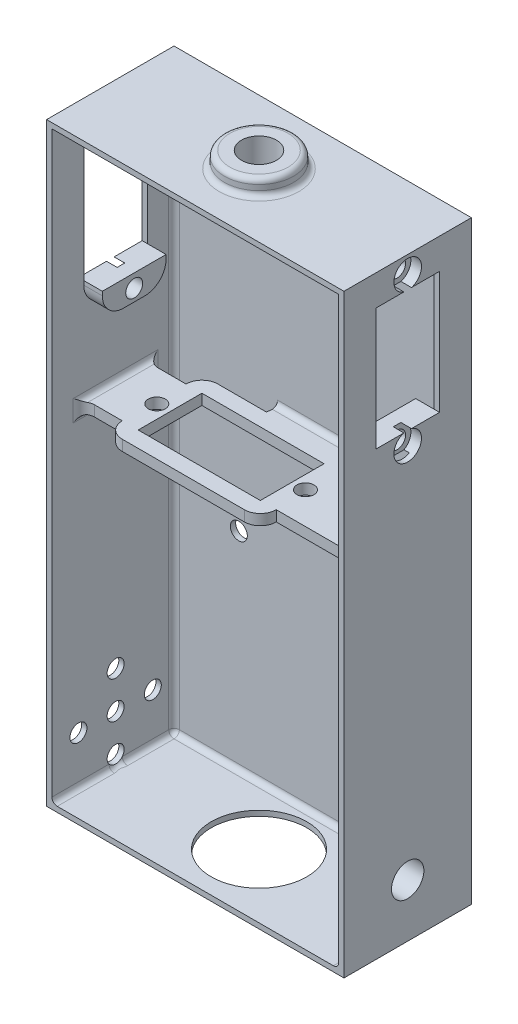
SolidWorks part; units mm, degrees
ref_plane "前视基准面" through (0, 0, 0) normal (0, 0, 1) x (1, 0, 0)
ref_plane "上视基准面" through (0, 0, 0) normal (0, 1, 0) x (1, 0, 0)
ref_plane "右视基准面" through (0, 0, 0) normal (1, 0, 0) x (0, 0, -1)
other "Configuration Table"
sketch "草图2" plane through (0, 0, 0) normal (0, 1, 0) x (1, 0, 0)
  line L1 (-28, 12) -> (28, 12)
  line L2 (-28, 12) -> (-28, -12)
  line L3 (-28, -12) -> (28, -12)
  line L4 (28, 12) -> (28, -12)
  line L5 (-28, 12) -> (28, -12) construction
  line L6 (-28, -12) -> (28, 12) construction
  point P0 (0, 0)
  dimension "D1" = 24
  dimension "D2" = 56
extrude "凸台-拉伸1" add sketch "草图2" along normal blind 72
shell "抽壳1" thickness 1
sketch "草图4" plane through (28, 0, 0) normal (1, 0, 0) x (0, 0, -1)
  line L0 (-27.2895, 60) -> (31.8558, 60) construction
  line L1 (0, 79.8899) -> (0, -4.7394) construction
  line L2 (-12, 72) -> (12, 72) construction
  line L4 (-6, 43.25) -> (6, 43.25)
  line L5 (-6, 43.25) -> (-6, 66.25)
  line L6 (-6, 66.25) -> (6, 66.25)
  line L7 (6, 43.25) -> (6, 66.25)
  line L8 (-6, 43.25) -> (6, 66.25) construction
  line L9 (-6, 66.25) -> (6, 43.25) construction
  point P7 (0, 60)
  point P8 (0, 54.75)
  dimension "D1" = 12
  dimension "D2" = 12
  dimension "D3" = 23
  dimension "D4" = 5.25
extrude "切除-拉伸1" cut sketch "草图4" against normal up to next
sketch "草图5" plane through (27, 0, 0) normal (-1, 0, 0) x (0, 0, 1)
  line L0 (-18.0719, 54.75) -> (26.0629, 54.75) construction
  line L1 (-6, 66.25) -> (-6, 67)
  line L2 (12, 71) -> (-11, 71) construction
  line L3 (-2, 71) -> (2, 71)
  line L4 (-6, 43.25) -> (6, 43.25)
  line L5 (-6, 66.25) -> (-6, 43.25)
  line L6 (6, 66.25) -> (-6, 66.25)
  line L7 (6, 43.25) -> (6, 66.25)
  line L8 (-6, 43.25) -> (6, 43.25)
  line L9 (-6, 66.25) -> (-6, 43.25)
  line L10 (6, 66.25) -> (-6, 66.25)
  line L11 (6, 43.25) -> (6, 66.25)
  line L12 (6, 67) -> (6, 66.25)
  line L13 (6, 42.5) -> (6, 43.25)
  line L14 (-2, 38.5) -> (2, 38.5)
  line L15 (-6, 43.25) -> (-6, 42.5)
  circle A0 centre (0, 68.75) radius 1.6
  circle A1 centre (0, 40.75) radius 1.6
  arc A2 (6, 42.5) -> (2, 38.5) centre (2, 42.5) cw
  arc A3 (-2, 38.5) -> (-6, 42.5) centre (-2, 42.5) cw
  arc A4 (2, 71) -> (6, 67) centre (2, 67) cw
  arc A5 (-2, 71) -> (-6, 67) centre (-2, 67) ccw
  point P18 (6, 38.5)
  point P21 (-6, 38.5)
  point P24 (6, 71)
  point P27 (-6, 71)
  line M8 (-6, 66.25) -> (6, 66.25)
  line M10 (6, 43.25) -> (-6, 43.25)
  line M13 (12, 71) -> (-11, 71)
  dimension "D2" = 28
  dimension "D3" = 4
  dimension "D4" = 3.2
  dimension "D1" = 0
extrude "凸台-拉伸2" add sketch "草图5" along normal blind 4.5 from surface at -1 contours A5 L1 L12 A4 A0 M13 M8 | A3 L14 A2 L13 L15 A1 M10 starting at face at (28, 54.75, 0)
sketch "草图6" plane through (28, 0, 0) normal (1, 0, 0) x (0, 0, -1)
  line L0 (-6, 66.25) -> (6, 66.25) construction
  line L1 (-6, 43.25) -> (-6, 66.25) construction
  line L2 (6, 66.25) -> (6, 67) construction
  line L3 (2, 71) -> (-2, 71) construction
  line L4 (-6, 67) -> (-6, 66.25) construction
  line L5 (6, 43.25) -> (-6, 43.25) construction
  line L6 (-6, 42.5) -> (-6, 43.25) construction
  line L7 (2, 38.5) -> (-2, 38.5) construction
  line L8 (6, 43.25) -> (6, 42.5) construction
  line L9 (6, 66.25) -> (6, 43.25) construction
  line L10 (-6, 66.25) -> (6, 66.25)
  line L11 (-6, 43.25) -> (-6, 66.25)
  line L12 (6, 66.25) -> (6, 67)
  line L13 (2, 71) -> (-2, 71)
  line L14 (-6, 67) -> (-6, 66.25)
  line L15 (6, 43.25) -> (-6, 43.25)
  line L16 (-6, 42.5) -> (-6, 43.25)
  line L17 (2, 38.5) -> (-2, 38.5)
  line L18 (6, 43.25) -> (6, 42.5)
  line L19 (6, 66.25) -> (6, 43.25)
  arc A0 (6, 67) -> (2, 71) centre (2, 67) ccw construction
  circle A1 centre (0, 40.75) radius 1.6
  circle A2 centre (0, 40.75) radius 1.6
  circle A3 centre (0, 68.75) radius 1.6
  circle A4 centre (0, 68.75) radius 1.6
  arc A5 (-2, 71) -> (-6, 67) centre (-2, 67) ccw construction
  arc A6 (-6, 42.5) -> (-2, 38.5) centre (-2, 42.5) ccw construction
  arc A7 (2, 38.5) -> (6, 42.5) centre (2, 42.5) ccw construction
  arc A8 (6, 67) -> (2, 71) centre (2, 67) ccw
  arc A9 (-2, 71) -> (-6, 67) centre (-2, 67) ccw
  arc A10 (-6, 42.5) -> (-2, 38.5) centre (-2, 42.5) ccw
  arc A11 (2, 38.5) -> (6, 42.5) centre (2, 42.5) ccw
  circle A12 centre (0, 68.75) radius 2.6
  circle A13 centre (0, 40.75) radius 2.6
  dimension "D3" = 5.2
  dimension "D4" = 5.2
  dimension "D1" = 0
  dimension "D2" = 0
extrude "切除-拉伸2" cut sketch "草图6" against normal blind 2 contours A12 | A13
sketch "草图7" plane through (-28, 0, 0) normal (-1, 0, 0) x (0, 0, 1)
  line L0 (6, 66.25) -> (-6, 66.25) construction
  line L1 (6, 43.25) -> (6, 66.25) construction
  line L2 (-6, 66.25) -> (-6, 67) construction
  line L3 (-2, 71) -> (2, 71) construction
  line L4 (6, 67) -> (6, 66.25) construction
  line L5 (-6, 43.25) -> (6, 43.25) construction
  line L6 (6, 42.5) -> (6, 43.25) construction
  line L7 (-2, 38.5) -> (2, 38.5) construction
  line L8 (-6, 43.25) -> (-6, 42.5) construction
  line L9 (-6, 66.25) -> (-6, 43.25) construction
  line L10 (6, 66.25) -> (-6, 66.25)
  line L11 (6, 43.25) -> (6, 66.25)
  line L12 (-6, 66.25) -> (-6, 67)
  line L13 (-2, 71) -> (2, 71)
  line L14 (6, 67) -> (6, 66.25)
  line L15 (-6, 43.25) -> (6, 43.25)
  line L16 (6, 42.5) -> (6, 43.25)
  line L17 (-2, 38.5) -> (2, 38.5)
  line L18 (-6, 43.25) -> (-6, 42.5)
  line L19 (-6, 66.25) -> (-6, 43.25)
  arc A0 (-2, 71) -> (-6, 67) centre (-2, 67) ccw construction
  circle A1 centre (0, 40.75) radius 1.6
  circle A2 centre (0, 40.75) radius 1.6
  circle A3 centre (0, 68.75) radius 1.6
  circle A4 centre (0, 68.75) radius 1.6
  arc A5 (6, 67) -> (2, 71) centre (2, 67) ccw construction
  arc A6 (2, 38.5) -> (6, 42.5) centre (2, 42.5) ccw construction
  arc A7 (-6, 42.5) -> (-2, 38.5) centre (-2, 42.5) ccw construction
  arc A8 (-2, 71) -> (-6, 67) centre (-2, 67) ccw
  arc A9 (6, 67) -> (2, 71) centre (2, 67) ccw
  arc A10 (2, 38.5) -> (6, 42.5) centre (2, 42.5) ccw
  arc A11 (-6, 42.5) -> (-2, 38.5) centre (-2, 42.5) ccw
  dimension "D1" = 0
  dimension "D2" = 0
extrude "凸台-拉伸3" add sketch "草图7" against normal blind 4.5
mirror "镜向1" about plane through (0, 0, 0) normal (1, 0, 0) of "切除-拉伸1", "切除-拉伸2"
sketch "草图8" plane through (0, 72, 0) normal (0, 1, 0) x (1, 0, 0)
  circle A0 centre (0, 0) radius 3.3
  circle A1 centre (0, 0) radius 6.5
  dimension "D1" = 6.6
  dimension "D2" = 13
ref_plane "基准面1" through (0, 22, 0) normal (0, 1, 0) x (1, 0, 0)
sketch "草图12" plane through (0, 22, 0) normal (0, 1, 0) x (1, 0, 0)
  line L0 (-5.25, -18.0719) -> (-5.25, 26.0629) construction
  line L1 (-16.75, -6) -> (-17.5, -6)
  line L2 (-21.5, -2) -> (-21.5, 2)
  line L3 (6.25, -6) -> (6.25, 6)
  line L4 (-16.75, -6) -> (6.25, -6)
  line L5 (-16.75, 6) -> (-16.75, -6)
  line L6 (-11.5, 6) -> (-16.75, 6)
  line L7 (-17.5, 6) -> (-16.75, 6)
  line L8 (7, 6) -> (6.25, 6)
  line L9 (11, -2) -> (11, 2)
  line L10 (6.25, -6) -> (7, -6)
  line L11 (-32.694, 0) -> (35.5884, 0) construction
  line L12 (27, -12) -> (27, 11) construction
  line L13 (27, 11) -> (-27, 11) construction
  line L14 (-27, 11) -> (-27, -12) construction
  line L15 (27, 8) -> (27, 11)
  line L16 (27, 11) -> (-27, 11)
  line L17 (-27, 11) -> (-27, 8)
  line L18 (-17.5, -6) -> (-25, -6)
  line L19 (-16.75, 6) -> (-25, 6)
  line L20 (11.5, 6) -> (25, 6)
  line L21 (6.25, -6) -> (25, -6)
  line L22 (-7.5, 11) -> (-7.5, 10)
  line L23 (0, -13.2) -> (0, 13.2) construction
  line L24 (7.5, 11) -> (7.5, 10)
  line L25 (-27, -12) -> (-27, -8)
  line L26 (27, -12) -> (27, -8)
  line L27 (-28, -12) -> (28, -12) construction
  line L28 (-27, -8) -> (-27, 8)
  line L29 (27, -8) -> (27, 8)
  line L30 (6.25, 6) -> (-11.5, 6)
  line L31 (-11.5, 9) -> (-16.75, 9)
  line L32 (6.25, 9) -> (-11.5, 9)
  line L33 (9.25, -6) -> (9.25, 6)
  line L34 (-16.75, -9) -> (6.25, -9)
  line L35 (-19.75, 6) -> (-19.75, -6)
  line L36 (6.25, 9) -> (-11.5, 9) construction
  line L37 (9.25, -6) -> (9.25, 6) construction
  line L38 (-16.75, -9) -> (6.25, -9) construction
  line L39 (-19.75, 6) -> (-19.75, -6) construction
  line L40 (-11.5, 9) -> (-16.75, 9) construction
  circle A0 centre (-19.25, 0) radius 1.6
  circle A1 centre (8.75, 0) radius 1.6
  arc A2 (7, 6) -> (11, 2) centre (7, 2) cw
  arc A3 (11, -2) -> (7, -6) centre (7, -2) cw
  arc A4 (-21.5, 2) -> (-17.5, 6) centre (-17.5, 2) cw
  arc A5 (-21.5, -2) -> (-17.5, -6) centre (-17.5, -2) ccw
  arc A6 (11.5, 6) -> (7.5, 10) centre (11.5, 10) cw
  arc A7 (-11.5, 6) -> (-7.5, 10) centre (-11.5, 10) ccw
  arc A8 (-27, 8) -> (-25, 6) centre (-25, 8) ccw
  arc A9 (27, 8) -> (25, 6) centre (25, 8) cw
  arc A10 (27, -8) -> (25, -6) centre (25, -8) ccw
  arc A11 (-27, -8) -> (-25, -6) centre (-25, -8) cw
  arc A12 (6.25, 9) -> (9.25, 6) centre (6.25, 6) cw
  arc A13 (9.25, -6) -> (6.25, -9) centre (6.25, -6) cw
  arc A14 (-16.75, -9) -> (-19.75, -6) centre (-16.75, -6) cw
  arc A15 (-19.75, 6) -> (-16.75, 9) centre (-16.75, 6) cw
  dimension "D2" = 4
  dimension "D3" = 3.2
  dimension "D8" = 4
  dimension "D9" = 2
  dimension "D10" = 2
  dimension "D12" = 3
  dimension "D1" = 28
  dimension "D4" = 5.25
  dimension "D5" = 23
  dimension "D6" = 12
  dimension "D7" = 15
  dimension "D11" = 3
  dimension "D13" = 32.5
extrude "凸台-拉伸7" add sketch "草图12" along normal blind 2 contours L28 A11 L18 A5 L2 A4 L19 A8 | A10 L29 A9 L20 A6 L24 L16 L22 A7 L6 L5 L4 L3 L8 A2 L9 A3 L21 | L2 A5 L1 L5 L7 A4 A0 | A3 L9 A2 L8 L3 L10 A1 | L2 A5 L35 A0 A4 | A14 L34 A13 L21 L10 L4 L1 L18 | A15 L19 L7 L6 A7 L32 L31 | L35 A4 L19 | A12 L32 A7 L30 L8 A2 L33 A6 | A3 L9 A2 L33 A1 | A12 A6 | L33 A3 L21 | A5 L35 L18 | L32 A12 A6 L24 L16 L22 A7
fillet "圆角3" radius 1 6 edges at (27, 24, 0) (27, 22, 0) (0, 24, -11) (0, 22, -11) (-27, 24, 0) (-27, 22, 0)
sketch "草图13" plane through (0, 72, 0) normal (0, 1, 0) x (1, 0, 0)
  line L0 (0, 0) -> (9.25, 16.0215)
  line L1 (0, 0) -> (13.0815, -13.0815)
  line L2 (0, 45.1895) -> (0, -6.9245)
  line L3 (-28, -12) -> (28, -12) construction
  line L4 (28, 12) -> (-28, 12) construction
  line L5 (-28, -12) -> (28, -12)
  line L6 (28, 12) -> (-28, 12)
  line L7 (28, 10.5) -> (-28, 10.5)
  line L8 (-28, -10.5) -> (28, -10.5)
  circle A2 centre (0, 0) radius 12.5
  circle A3 centre (0, 0) radius 18.5
  dimension "D1" = 25
  dimension "D2" = 6
  dimension "D3" = 30
  dimension "D4" = 45
  dimension "D5" = 1.5
extrude "切除-拉伸5" [suppressed] cut sketch "草图13" against normal up to next contours L8 A3 L7 A2 L1 | A2 L8 L1
sketch "草图14" plane through (0, 0, 0) normal (0, -1, 0) x (1, 0, 0)
  line L8 (28, 12) -> (27, 12)
  line L9 (27, 12) -> (27, -11)
  line L10 (27, -11) -> (-27, -11)
  line L11 (-27, -11) -> (-27, 12)
  line L12 (-27, 12) -> (-28, 12)
  line L13 (-28, 12) -> (-28, -12)
  line L14 (-28, -12) -> (28, -12)
  line L15 (28, -12) -> (28, 12)
  line L16 (28, 12) -> (27, 12)
  line L17 (27, 12) -> (27, -11)
  line L18 (27, -11) -> (-27, -11)
  line L19 (-27, -11) -> (-27, 12)
  line L20 (-27, 12) -> (-28, 12)
  line L21 (-28, 12) -> (-28, -12)
  line L22 (-28, -12) -> (28, -12)
  line L23 (28, -12) -> (28, 12)
  dimension "D1" = 0
extrude "凸台-拉伸8" add sketch "草图14" along normal blind 40
sketch "草图15" plane through (0, -40, 0) normal (0, -1, 0) x (1, 0, 0)
  line L1 (-28, 12) -> (28, 12)
  line L2 (-28, 12) -> (-28, -12)
  line L3 (-28, -12) -> (28, -12)
  line L4 (28, 12) -> (28, -12)
  circle A0 centre (0, 0) radius 9
extrude "凸台-拉伸9" add sketch "草图15" against normal blind 1
sketch "草图16" plane through (-28, 0, 0) normal (-1, 0, 0) x (0, 0, 1)
  line L0 (0, -30.8) -> (0, 30.8) construction
  line L1 (12, -40) -> (-12, -40) construction
  circle A0 centre (0, -30) radius 7.0004 construction
  circle A1 centre (-7.0004, -30) radius 1.6
  circle A2 centre (0, -22.9996) radius 1.6
  circle A3 centre (7.0004, -30) radius 1.6
  circle A4 centre (0, -37.0004) radius 1.6
  circle A5 centre (0, -30) radius 1.6
  dimension "D1" = 3.2
  dimension "D2" = 4
  dimension "D5" = 3.2
  dimension "D3" = 9.9
  dimension "D4" = 10
extrude "切除-拉伸6" cut sketch "草图16" against normal up to next
fillet "圆角4" radius 1 6 edges at (27, 16, -11) (-27, 16, -11) (0, 71, -11) (0, -39, -11) (-27, -39, 0.5) (27, -39, 0.5)
sketch "草图17" plane through (28, 0, 0) normal (1, 0, 0) x (0, 0, -1)
  circle A0 centre (0, -30) radius 1.6 construction
  circle A1 centre (0, -30) radius 1.6
  circle A2 centre (0, -30) radius 3.05
  dimension "D1" = 6.1
extrude "切除-拉伸7" cut sketch "草图17" against normal up to next contours A2
sketch "草图18" plane through (27, 0, 0) normal (-1, 0, 0) x (0, 0, 1)
  circle A0 centre (0, -30) radius 5.05
  circle A1 centre (0, -30) radius 3.05
  circle A2 centre (0, -30) radius 3.05
  circle A3 centre (0, -30) radius 1.6
  circle A4 centre (0, -30) radius 1.6
  circle M4 centre (0, -30) radius 3.05
  dimension "D3" = 2
  dimension "D1" = 0
  dimension "D2" = 0
extrude "凸台-拉伸10" add sketch "草图18" along normal blind 4 contours A0 M4
fillet "圆角5" radius 1 2 edges at (27, -30, 5.05) (23, -30, 5.05)
extrude "凸台-拉伸11" add sketch "草图8" along normal blind 3 and the other way blind 4 contours A0 | A1 A0
sketch "草图20" plane through (0, 72, 0) normal (0, 1, 0) x (1, 0, 0)
  circle A1 centre (0, 0) radius 6.5
  circle A2 centre (0, 0) radius 6.5
  circle A3 centre (0, 0) radius 3.3
  circle A4 centre (0, 0) radius 3.3
  dimension "D1" = 0
  dimension "D2" = 0
extrude "切除-拉伸8" cut sketch "草图20" against normal mid plane 20 contours A4
fillet "圆角6" radius 1 4 edges at (0, 72, 6.5) (0, 71, 6.5) (0, 68, 6.5) (0, 75, 6.5)
sketch "草图21" plane through (0, 0, -12) normal (0, 0, -1) x (-1, 0, 0)
  line L0 (0, 82.2912) -> (0, -75.2684) construction
  line L1 (28, -40) -> (-28, -40) construction
  circle A0 centre (-14.8, 0) radius 1.6
  circle A1 centre (14.8, 0) radius 1.6
  dimension "D1" = 3.2
  dimension "D2" = 40
  dimension "D3" = 29.6
extrude "切除-拉伸9" cut sketch "草图21" against normal mid plane 20
